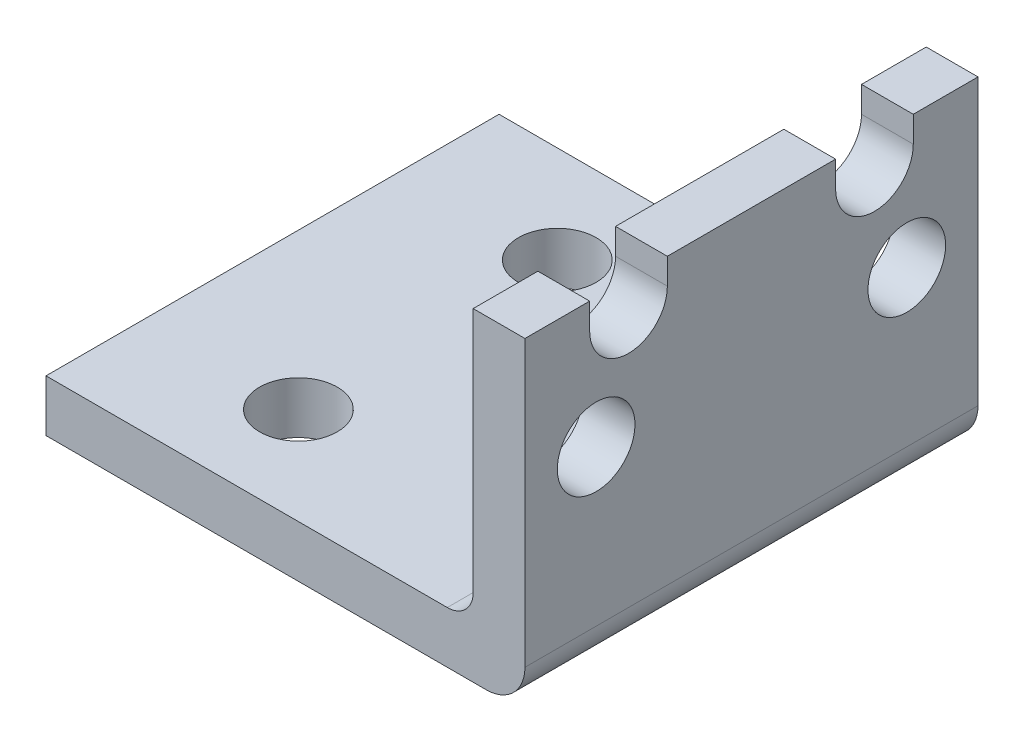
SolidWorks part; units mm, degrees
ref_plane "前视基准面" through (0, 0, 0) normal (0, 0, 1) x (1, 0, 0)
ref_plane "上视基准面" through (0, 0, 0) normal (0, 1, 0) x (1, 0, 0)
ref_plane "右视基准面" through (0, 0, 0) normal (1, 0, 0) x (0, 0, -1)
sketch "草图1" plane through (0, 0, 0) normal (0, 0, 1) x (1, 0, 0)
  line L0 (24.1676, -0.0793) -> (24.1676, -22.0793)
  line L1 (21.1676, -25.0793) -> (-12.8324, -25.0793)
  line L2 (20.1676, -0.0793) -> (20.1676, -19.0793)
  line L3 (18.1676, -21.0793) -> (-12.8324, -21.0793)
  line L4 (20.1676, -0.0793) -> (24.1676, -0.0793)
  line L5 (24.1676, -0.0793) -> (24.4068, -0.134)
  line L6 (-12.8324, -25.0793) -> (-12.8324, -21.0793)
  line L7 (24.1676, -25.0793) -> (-12.8324, -25.0793) construction
  line L8 (24.1676, -0.0793) -> (24.1676, -25.0793) construction
  line L9 (20.1676, -21.0793) -> (-12.8324, -21.0793) construction
  line L10 (20.1676, -0.0793) -> (20.1676, -21.0793) construction
  arc A0 (21.1676, -25.0793) -> (24.1676, -22.0793) centre (21.1676, -22.0793) ccw
  arc A1 (18.1676, -21.0793) -> (20.1676, -19.0793) centre (18.1676, -19.0793) ccw
  point P10 (24.1676, -25.0793)
  dimension "D4" = 3
  dimension "D5" = 2
  dimension "D1" = 25
  dimension "D2" = 37
  dimension "D3" = 4
extrude "拉伸1" add sketch "草图1" along normal blind 35 contours A1 L3 L6 L1 A0 L0 L4 L2 region at (23.7211, -11.0793, 0)
sketch "草图2" plane through (0, -25.0793, 0) normal (0, -1, 0) x (1, 0, 0)
  line L0 (21.1676, 0) -> (-12.8324, 0) construction
  line L1 (24.1676, 35) -> (24.1676, 0) construction
  circle A0 centre (-0.8324, 7.5) radius 3
  circle A1 centre (-0.8324, 27.5) radius 3
  dimension "D1" = 6
  dimension "D2" = 6
  dimension "D3" = 20
  dimension "D4" = 7.5
  dimension "D5" = 25
extrude "拉伸2" cut sketch "草图2" against normal blind 35
sketch "草图3" plane through (24.1676, 0, 0) normal (1, 0, 0) x (0, 0, -1)
  line L0 (-35, -0.0793) -> (-35, -19.0793) construction
  line L2 (-35, -25.0793) -> (0, -25.0793) construction
  line L3 (0, -0.0793) -> (0, -19.0793) construction
  line L4 (-35, -0.0793) -> (0, -0.0793) construction
  line L5 (-5, -2.0793) -> (-5, 0.4555)
  line L6 (-11, -2.0793) -> (-11, 0.4555)
  line L7 (-24, -2.0793) -> (-24, 0.4555)
  line L8 (-30, -2.0793) -> (-30, 0.4555)
  line L9 (-5, 0.4555) -> (-11, 0.4555)
  line L10 (-24, 0.4555) -> (-30, 0.4555)
  circle A0 centre (-5.5, -10.0793) radius 3
  circle A1 centre (-29.5, -10.0793) radius 3
  arc A2 (-11, -2.0793) -> (-5, -2.0793) centre (-8, -2.0793) ccw
  arc A3 (-30, -2.0793) -> (-24, -2.0793) centre (-27, -2.0793) ccw
  dimension "D1" = 6
  dimension "D2" = 6
  dimension "D3" = 24
  dimension "D4" = 5.5
  dimension "D5" = 15
  dimension "D6" = 15
  dimension "D7" = 6
  dimension "D8" = 6
  dimension "D9" = 19
  dimension "D10" = 8
  dimension "D11" = 2
extrude "拉伸4" add sketch "草图3" against normal through all
extrude "拉伸5" cut sketch "草图3<2>" against normal through all
sketch "草图3<2>" plane through (24.1676, 0, 0) normal (1, 0, 0) x (0, 0, -1) same geometry as "草图3"
